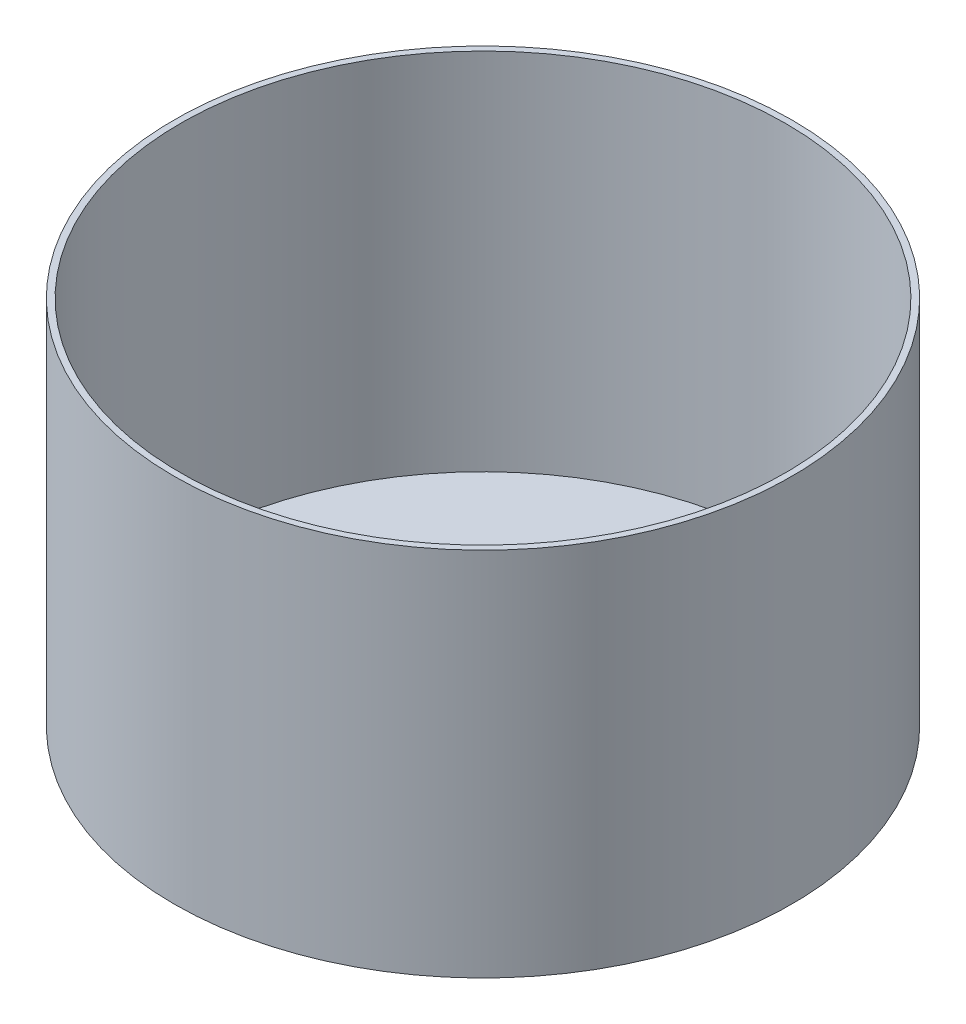
SolidWorks part; units mm, degrees
ref_plane "Front" through (0, 0, 0) normal (0, 0, 1) x (1, 0, 0)
ref_plane "Top" through (0, 0, 0) normal (0, 1, 0) x (1, 0, 0)
ref_plane "Right" through (0, 0, 0) normal (1, 0, 0) x (0, 0, -1)
sketch "Sketch1" plane through (0, 0, 0) normal (0, 1, 0) x (1, 0, 0)
  circle A0 centre (0, 0) radius 127
  dimension "D1" = 254
extrude "Boss-Extrude1" add sketch "Sketch1" along normal blind 152.4
shell "Shell1" thickness 2.54 removed face at (0, 152.4, 127)
